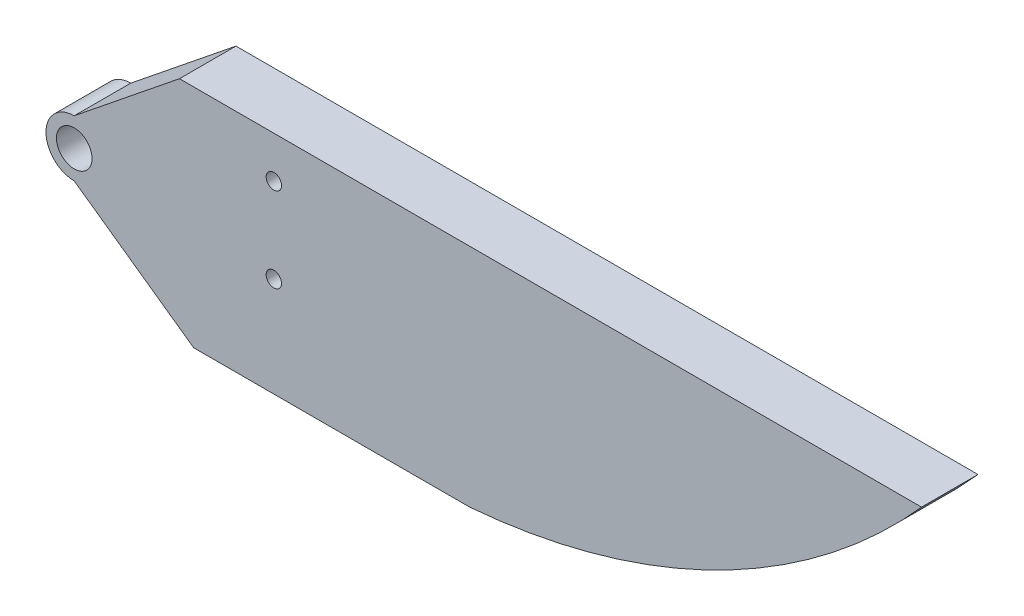
SolidWorks part; units mm, degrees
ref_plane "Front Plane" through (0, 0, 0) normal (0, 0, 1) x (1, 0, 0)
ref_plane "Top Plane" through (0, 0, 0) normal (0, 1, 0) x (1, 0, 0)
ref_plane "Right Plane" through (0, 0, 0) normal (1, 0, 0) x (0, 0, -1)
sketch "Sketch1" plane through (0, 0, 0) normal (0, 0, 1) x (1, 0, 0)
  line L1 (101.6, 25.4) -> (-101.6, 25.4)
  line L2 (101.6, 25.4) -> (101.6, -25.4)
  line L3 (101.6, -25.4) -> (-101.6, -25.4)
  line L4 (-101.6, 25.4) -> (-101.6, -25.4)
  line L5 (101.6, 25.4) -> (-101.6, -25.4) construction
  line L6 (101.6, -25.4) -> (-101.6, 25.4) construction
  point P0 (0, 0)
  dimension "D1" = 203.2
  dimension "D2" = 50.8
extrude "Boss-Extrude1" add sketch "Sketch1" along normal blind 12.7
sketch "Sketch3" plane through (0, 0, 12.7) normal (0, 0, 1) x (1, 0, 0)
  line L0 (0, 0) -> (-101.6, 0) construction
  line L1 (-101.6, 25.4) -> (-101.6, -25.4) construction
  circle A0 centre (-88.9, 0) radius 4
  dimension "D2" = 8
  dimension "D1" = 12.7
extrude "Cut-Extrude1" cut sketch "Sketch3" against normal through all
sketch "Sketch5" plane through (0, 0, 12.7) normal (0, 0, 1) x (1, 0, 0)
  line L0 (-101.6, -25.4) -> (101.6, -25.4) construction
  line L1 (-88.9, -6.35) -> (-62.0461, -25.4)
  line L2 (-88.9, 6.35) -> (-65.2393, 25.4)
  line L3 (101.6, 25.4) -> (-101.6, 25.4) construction
  line L4 (-65.2393, 25.4) -> (-101.6, 25.4)
  line L5 (-101.6, 25.4) -> (-101.6, -25.4)
  line L6 (-101.6, -25.4) -> (-62.0461, -25.4)
  line L7 (101.6, 25.4) -> (101.6, -25.4)
  line L8 (101.6, -25.4) -> (0, -25.4)
  arc A0 (0, -25.4) -> (101.6, 25.4) centre (-12.4455, 126.491) ccw
  arc A2 (-88.9, 6.35) -> (-88.9, -6.35) centre (-88.9, 0) ccw
  dimension "D1" = 152.4
  dimension "D2" = 12.7
extrude "Cut-Extrude2" cut sketch "Sketch5" against normal through all
sketch "Sketch6" plane through (0, 0, 12.7) normal (0, 0, 1) x (1, 0, 0)
  line L0 (-88.9, 0) -> (72.5592, 0) construction
  arc A0 (0, -25.4) -> (101.6, 25.4) centre (-12.4455, 126.491) ccw construction
  circle A1 centre (38.1, 0) radius 3.1347
  dimension "D1" = 127
sketch "Sketch7" plane through (0, 0, 0) normal (0, 0, -1) x (-1, 0, 0)
  line L0 (44.0204, -2.9977) -> (44.0204, 16.0523) construction
  point P3 (44.0204, -2.9977)
  point P4 (44.0204, 16.0523)
  dimension "D1" = 19.05
sketch "Sketch8" plane through (0, 0, 0) normal (0, 0, -1) x (-1, 0, 0)
  point P0 (44.0204, 16.0523)
  point P3 (44.0204, -2.9977)
hole_wizard "Tap Drill for #8-32 Tap1" positions "Sketch8" profile "Sketch9" hole size "#8-32" standard "ANSI Inch" end condition through all
sketch "Sketch9" plane through (-44.0204, 16.0523, 0) normal (1, 0, 0) x (0, 1, 0)
  line L0 (0, 0) -> (0, 12.7)
  line L1 (0, 12.7) -> (1.7272, 12.7)
  line L2 (1.7272, 12.7) -> (1.7272, 0)
  line L5 (1.7272, 0) -> (0, 0)
  line L11 (0, -6.35) -> (0, 107.95) construction
  dimension "Thru Hole Dia." = 3.4544
  dimension "Thru Hole Depth" = 12.7
